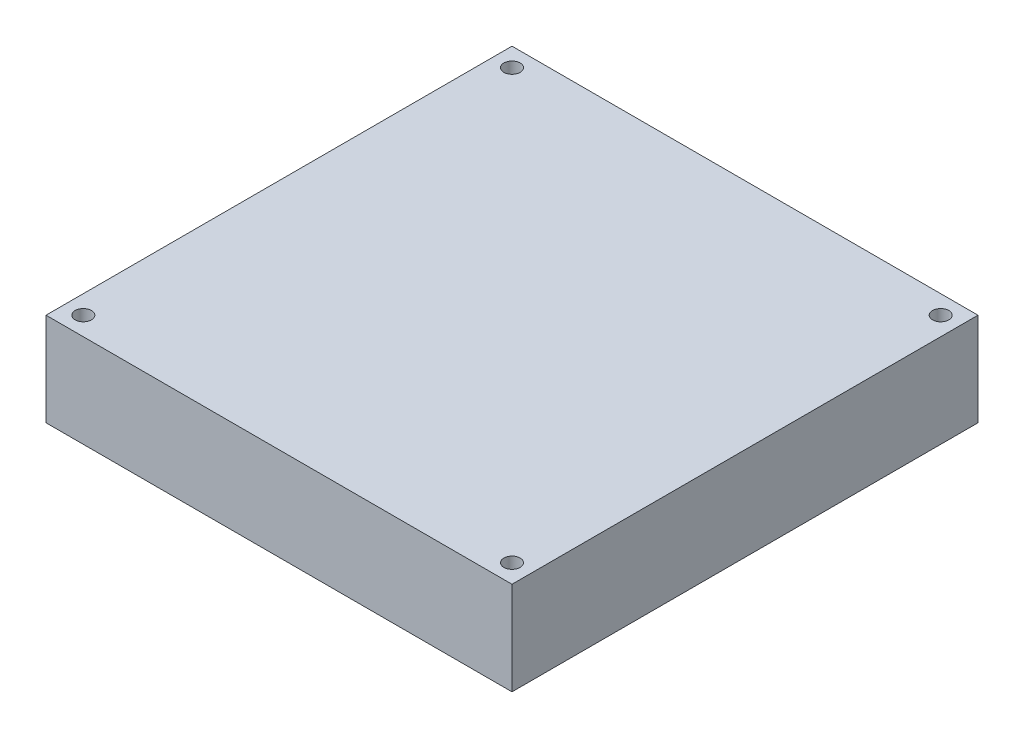
SolidWorks part; units mm, degrees
ref_plane "Front Plane" through (0, 0, 0) normal (0, 0, 1) x (1, 0, 0)
ref_plane "Top Plane" through (0, 0, 0) normal (0, 1, 0) x (1, 0, 0)
ref_plane "Right Plane" through (0, 0, 0) normal (1, 0, 0) x (0, 0, -1)
sketch "Sketch1" plane through (0, 0, 0) normal (0, 1, 0) x (1, 0, 0)
  line L1 (-100, 100) -> (0, 100)
  line L2 (-100, 100) -> (-100, 0)
  line L3 (-100, 0) -> (0, 0)
  line L4 (0, 100) -> (0, 0)
  circle A0 centre (-96, 96) radius 1.75
  circle A1 centre (-96, 4) radius 1.75
  circle A2 centre (-4, 4) radius 1.75
  circle A3 centre (-4, 96) radius 1.75
  point P12 (0, 0)
  point P13 (0, 0)
  point P14 (0, 0)
  dimension "D3" = 3.5
  dimension "D1" = 100
  dimension "D2" = 100
  dimension "D4" = 4
  dimension "D5" = 4
  dimension "D6" = 4
  dimension "D7" = 4
  dimension "D8" = 4
  dimension "D9" = 4
  dimension "D10" = 4
  dimension "D11" = 4
extrude "Boss-Extrude1" add sketch "Sketch1" along normal blind 20
